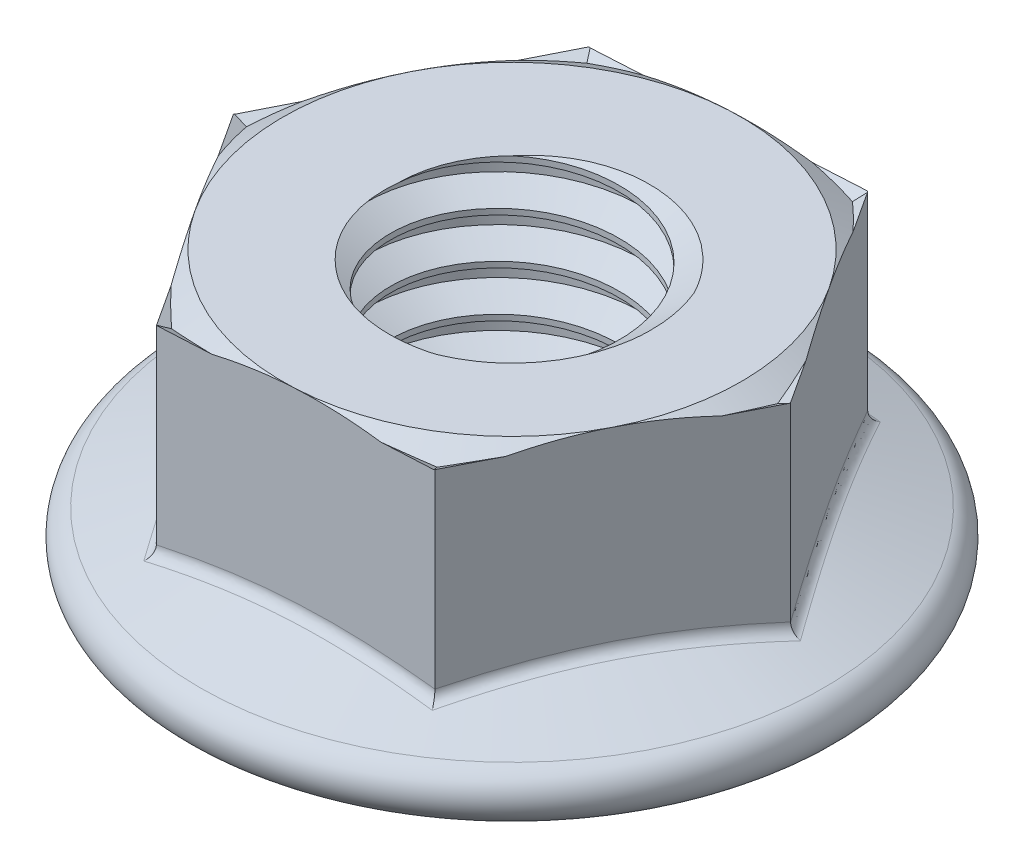
SolidWorks part; units mm, degrees
ref_plane "Front Plane" through (0, 0, 0) normal (0, 0, 1) x (1, 0, 0)
ref_plane "Top Plane" through (0, 0, 0) normal (0, 1, 0) x (1, 0, 0)
ref_plane "Right Plane" through (0, 0, 0) normal (1, 0, 0) x (0, 0, -1)
sketch "Sketch1" plane through (0, 0, 0) normal (0, 1, 0) x (1, 0, 0)
  line L1 (-5.765, -0.3128) -> (-2.6116, -5.149)
  line L2 (-2.6116, -5.149) -> (3.1534, -4.8363)
  line L3 (3.1534, -4.8363) -> (5.765, 0.3128)
  line L4 (5.765, 0.3128) -> (2.6116, 5.149)
  line L5 (2.6116, 5.149) -> (-3.1534, 4.8363)
  line L6 (-3.1534, 4.8363) -> (-5.765, -0.3128)
  circle A0 centre (0, 0) radius 5 construction
  circle A1 centre (0, 0) radius 2.5
  point P11 (0, 0)
  dimension "D1" = 10
  dimension "D2" = 2.5
extrude "Boss-Extrude1" add sketch "Sketch1" against normal blind 6
sketch "Sketch2" plane through (0, 0, 0) normal (0, 0, 1) x (1, 0, 0)
  line L0 (2.6116, -3.35) -> (2.6116, -6)
  line L1 (-2.6116, -6) -> (3.1534, -6) construction
  line L2 (2.6116, -6) -> (6.6116, -6)
  line L3 (6.8095, -4.8779) -> (2.6116, -3.35)
  line L5 (2.6116, -6) -> (2.6116, 0) construction
  arc A0 (6.6116, -6) -> (6.8095, -4.8779) centre (6.6116, -5.4215) ccw
  point P7 (2.6116, -3.35)
  point P9 (-10.0723, -4.5133)
  dimension "D3" = 20
  dimension "D1" = 2.65
  dimension "D2" = 4
revolve "Revolve1" add sketch "Sketch2" angle 360 about axis through (0, -6, 0) along (0, 1, 0)
sketch "Sketch4" plane through (0, 0, 0) normal (0, 1, 0) x (1, 0, 0)
  line L1 (-6.1112, -0.3128) -> (-2.7847, -5.4488)
  line L2 (-2.7847, -5.4488) -> (3.3265, -5.1361)
  line L3 (3.3265, -5.1361) -> (6.1112, 0.3128)
  line L4 (6.1112, 0.3128) -> (2.7847, 5.4488)
  line L5 (2.7847, 5.4488) -> (-3.3265, 5.1361)
  line L6 (-3.3265, 5.1361) -> (-6.1112, -0.3128)
  circle A0 centre (0, 0) radius 5
  circle A1 centre (0, 0) radius 5.2994 construction
extrude "Cut-Extrude4" cut sketch "Sketch4" against normal blind 6 draft 60
thread "Thread1" pitch 1 start angle 0, offset 1, length 0, pitch 1, diameter 5
ref_plane "Plane1" through (-2.5, 1, 0) normal (0, 0, -1) x (1, 0, 0)
sketch "Thread Profile1" plane through (-2.5, 1, 0) normal (0, 0, -1) x (1, 0, 0)
  line L0 (0, 0) -> (0, 1) construction
  line L11 (0, 0) -> (0, 0.875)
  line L12 (0, 0.875) -> (-0.5413, 0.5625)
  line L13 (-0.5413, 0.5625) -> (-0.5413, 0.3125)
  line L15 (-0.5413, 0.3125) -> (0, 0)
  line L17 (-0.5413, 0.4375) -> (0, 0.4375) construction
  point P2 (0, 0)
  dimension "Pitch" = 1
  dimension "Profile_Angle" = 60
  dimension "Profile_Land" = 0.25
  dimension "Profile_Height" = 0.5413
fillet "Fillet1" radius 0.25 6 edges
